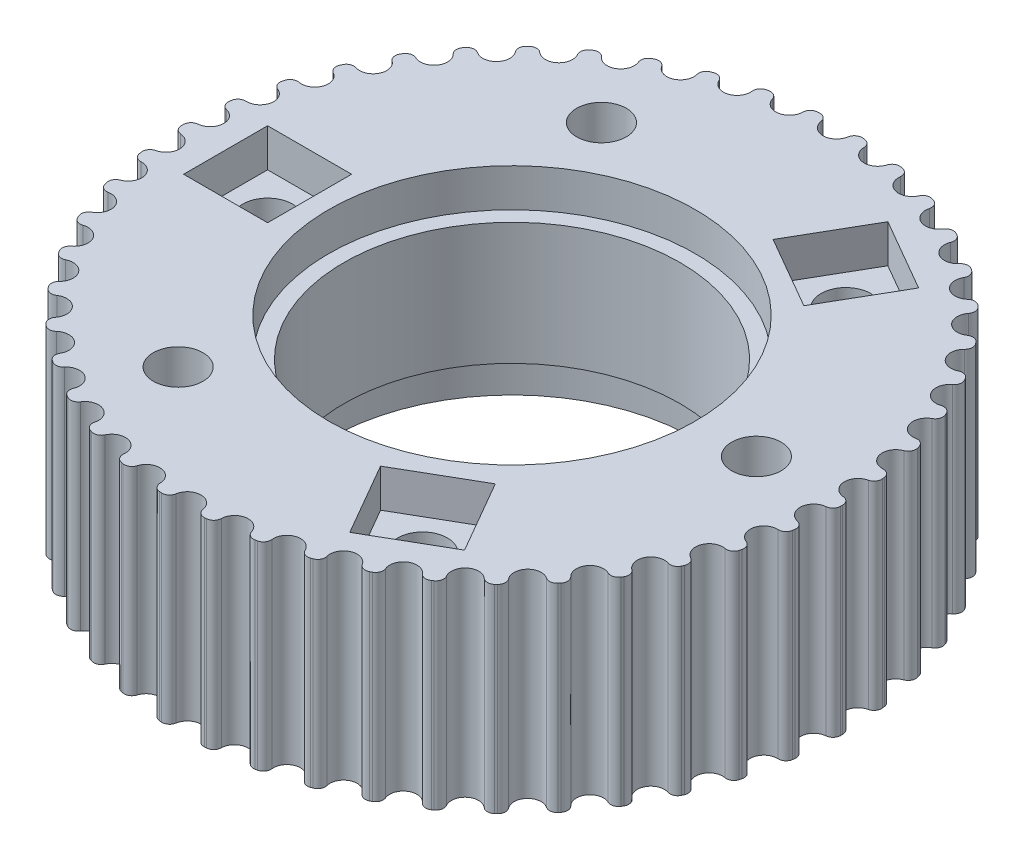
SolidWorks part; units mm, degrees
ref_plane "Front Plane" through (0, 0, 0) normal (0, 0, 1) x (1, 0, 0)
ref_plane "Top Plane" through (0, 0, 0) normal (0, 1, 0) x (1, 0, 0)
ref_plane "Right Plane" through (0, 0, 0) normal (1, 0, 0) x (0, 0, -1)
sketch "Sketch1" plane through (0, 0, 0) normal (0, 1, 0) x (1, 0, 0)
  line L0 (0, 0) -> (0, 21.582) construction
  line L1 (0, 0) -> (2.8938, 21.0541) construction
  circle A0 centre (0, 0) radius 21.582 construction
  circle A1 centre (0, 0) radius 20.362 construction
  circle A2 centre (0, 21.252) radius 0.89 construction
  circle A5 centre (2.8938, 21.0541) radius 0.89 construction
  arc A6 (0, 20.362) -> (0.8793, 21.1145) centre (0, 21.252) ccw
  arc A7 (0.8793, 21.1145) -> (1.4059, 21.5362) centre (1.3733, 21.0373) cw
  arc A8 (1.5397, 21.527) -> (2.004, 21.0376) centre (1.5041, 21.0283) cw
  arc A9 (2.7726, 20.1724) -> (2.004, 21.0376) centre (2.8938, 21.0541) cw
  arc A10 (1.4059, 21.5362) -> (1.5397, 21.527) centre (0, 0) cw
  arc A11 (0, 20.362) -> (2.7726, 20.1724) centre (0, 0) ccw
  dimension "D1" = 43.1641
  dimension "D3" = 1.78
  dimension "D4" = 0.5
  dimension "D2" = 1.22
  dimension "D5" = 7.826
extrude "Boss-Extrude1" add sketch "Sketch1" along normal mid plane 13 contours A6 A11 A9 A8 A7 region at (0.0017, 0, -0.025)
ref_axis "Axis1" through (0, 3.3, 0) along (0, -1, 0)
pattern_circular "CirPattern1" count 46 over 360 about axis through (0, 3.3, 0) along (0, -1, 0) of "Boss-Extrude1"
sketch "Sketch2" plane through (0, 0, 0) normal (1, 0, 0) x (0, 0, -1)
  line L10 (0, 6.5) -> (22.7568, 6.5) construction
  line L11 (0, 6.5) -> (0, 8.0875) construction
  line L12 (0, 8.0875) -> (22.7568, 8.0875) construction
  line L15 (22.7568, 6.5) -> (22.7568, 8.0875) construction
  line L20 (0, 3.3) -> (0, -3.3) construction
  line L22 (22.7568, 8.0875) -> (0, 8.0875)
  line L23 (22.7568, 8.0875) -> (22.7568, 6.5)
  line L24 (22.7568, 6.5) -> (0, 6.5)
  line L25 (0, 8.0875) -> (0, 6.5)
  dimension "D1" = 1.5875
  dimension "D2" = 22.7568
  dimension "D3" = 6.5
revolve "Revolve3" [suppressed] add sketch "Sketch2" angle 360 about axis through (0, 3.3, 0) along (0, -1, 0)
mirror "Mirror1" [suppressed] about plane through (0, 0, 0) normal (0, 1, 0)
sketch "Sketch3" plane through (0, 0, 0) normal (0, -1, 0) x (-1, 0, 0)
  circle A0 centre (0, 0) radius 11
  dimension "D1" = 22
extrude "Cut-Extrude1" cut sketch "Sketch3" against normal through all both and the other way through all
sketch "Sketch4" plane through (0, 0, 0) normal (0, 1, 0) x (1, 0, 0)
  circle A0 centre (-16, 0) radius 1.625
  dimension "D1" = 3.25
extrude "Cut-Extrude2" cut sketch "Sketch4" against normal through all both and the other way through all
pattern_circular "CirPattern2" count 6 over 360 about axis through (0, 6.5, 0) along (0, -1, 0) of "Cut-Extrude2"
sketch "Sketch7" plane through (0, 0, 0) normal (0, 1, 0) x (1, 0, 0)
  circle A0 centre (0, 0) radius 12
  dimension "D1" = 24
extrude "Cut-Extrude3" cut sketch "Sketch7" along normal through all from offset 4
mirror "Mirror2" about plane through (0, 0, 0) normal (0, 1, 0) of "Cut-Extrude3"
sketch "Sketch8" plane through (0, -6.5, 0) normal (0, -1, 0) x (1, 0, 0)
  line L1 (13.25, 2.75) -> (18.75, 2.75)
  line L2 (13.25, 2.75) -> (13.25, -2.75)
  line L3 (13.25, -2.75) -> (18.75, -2.75)
  line L4 (18.75, 2.75) -> (18.75, -2.75)
  line L5 (13.25, 2.75) -> (18.75, -2.75) construction
  line L6 (13.25, -2.75) -> (18.75, 2.75) construction
  point P0 (16, 0)
  dimension "D1" = 5.5
extrude "Cut-Extrude4" cut sketch "Sketch8" against normal blind 2.5
sketch "Sketch9" plane through (0, 6.5, 0) normal (0, 1, 0) x (1, 0, 0)
  line L0 (18.75, -2.75) -> (13.25, -2.75) construction
  line L1 (-13.25, 2.75) -> (-18.75, 2.75)
  line L2 (-13.25, 2.75) -> (-13.25, -2.75)
  line L3 (-13.25, -2.75) -> (-18.75, -2.75)
  line L4 (-18.75, 2.75) -> (-18.75, -2.75)
  line L5 (-13.25, 2.75) -> (-18.75, -2.75) construction
  line L6 (-13.25, -2.75) -> (-18.75, 2.75) construction
  point P0 (-16, 0)
extrude "Cut-Extrude5" cut sketch "Sketch9" against normal blind 2.5
pattern_circular "CirPattern3" count 3 over 360 about axis through (0, 3.3, 0) along (0, -1, 0) of "Cut-Extrude4", "Cut-Extrude5"
equation "\"TEETH_NUM\"= 46"
equation "\"TOOTH_PITCH\"= 3mm"
equation "\"PITCH_LINE_OFFSET\"= .015in"
equation "\"DIAMETER_PER_GROOVE\"= \"OUTSIDE_DIAMETER\" / \"TEETH_NUM\" * 1in"
equation "\"PITCH_DIAMETER\"= ( ( \"TEETH_NUM\" * 3 - 1.31 ) / 3.1415 + .415 ) * 1mm"
equation "\"OUTSIDE_DIAMETER\"= \"PITCH_DIAMETER\" - \"PITCH_LINE_OFFSET\" * 2"
equation "\"D1@Sketch1\"=\"OUTSIDE_DIAMETER\""
equation "\"TOOTH_HEIGHT\"= 1.22mm"
equation "\"D2@Sketch1\"=\"TOOTH_HEIGHT\""
equation "\"TOOTH_DIAMETER\"= 1.78mm"
equation "\"INTERNAL_RADIUS\"= .5mm"
equation "\"D3@Sketch1\"=\"TOOTH_DIAMETER\""
equation "\"D5@Sketch1\"=360 / \"TEETH_NUM\""
equation "\"D4@Sketch1\"=\"INTERNAL_RADIUS\""
equation "\"D1@CirPattern1\"=\"TEETH_NUM\""
equation "\"BELT_GAP\"= 13mm"
equation "\"D2@Sketch2\"=\"PITCH_DIAMETER\"/2+1/32"
equation "\"D3@Sketch2\"=\"BELT_GAP\"/2"
equation "\"ID\"= \"bearing_OD\" - 2mm"
equation "\"D1@Sketch3\"=\"ID\""
equation "\"D1@Boss-Extrude1\"=\"BELT_GAP\""
equation "\"bearing_thickness\"= 5mm"
equation "\"Outside_Plate_Thickness\"= 2.5mm"
equation "\"Recess_Height\"= \"BELT_GAP\" / 2 + \"Outside_Plate_Thickness\" - \"bearing_thickness\""
equation "\"bearing_OD\"= 24mm"
equation "\"D1@Sketch7\"=\"bearing_OD\""
equation "\"D19@Cut-Extrude3\"=\"Recess_Height\""
